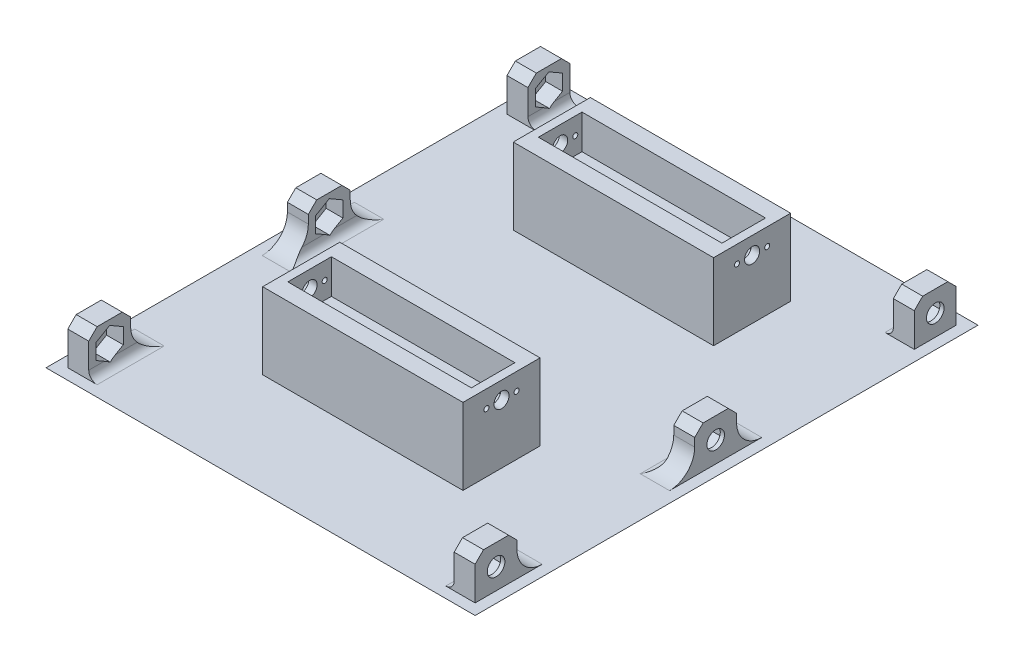
SolidWorks part; units mm, degrees
ref_plane "Front Plane" through (0, 0, 0) normal (0, 0, 1) x (1, 0, 0)
ref_plane "Top Plane" through (0, 0, 0) normal (0, 1, 0) x (1, 0, 0)
ref_plane "Right Plane" through (0, 0, 0) normal (1, 0, 0) x (0, 0, -1)
sketch "Sketch1" plane through (0, 0, 0) normal (0, 1, 0) x (1, 0, 0)
  line L1 (65.024, 76.2) -> (-65.024, 76.2)
  line L2 (65.024, 76.2) -> (65.024, -76.2)
  line L3 (65.024, -76.2) -> (-65.024, -76.2)
  line L4 (-65.024, 76.2) -> (-65.024, -76.2)
  line L5 (65.024, 76.2) -> (-65.024, -76.2) construction
  line L6 (65.024, -76.2) -> (-65.024, 76.2) construction
  point P0 (0, 0)
  dimension "D1" = 130.048
  dimension "D2" = 152.4
extrude "Boss-Extrude1" add sketch "Sketch1" along normal blind 2.54 contours L1 L4 L3 L2
chamfer "Chamfer1" distance 2.54 angle 45 4 edges at (0, 0, -76.2) (-65.024, 0, 0) (0, 0, 76.2) (65.024, 0, 0)
sketch "Sketch2" plane through (0, 2.54, 0) normal (0, 1, 0) x (1, 0, 0)
  line L1 (-27.813, 49.022) -> (27.813, 49.022)
  line L2 (-27.813, 49.022) -> (-27.813, 35.814)
  line L3 (-27.813, 35.814) -> (27.813, 35.814)
  line L4 (27.813, 49.022) -> (27.813, 35.814)
  line L5 (-27.813, 49.022) -> (27.813, 35.814) construction
  line L6 (-27.813, 35.814) -> (27.813, 49.022) construction
  line L7 (-27.813, -26.924) -> (27.813, -26.924)
  line L8 (-27.813, -26.924) -> (-27.813, -40.132)
  line L9 (-27.813, -40.132) -> (27.813, -40.132)
  line L10 (27.813, -26.924) -> (27.813, -40.132)
  line L11 (-27.813, -26.924) -> (27.813, -40.132) construction
  line L12 (-27.813, -40.132) -> (27.813, -26.924) construction
  line L13 (30.353, 54.102) -> (-30.353, 54.102)
  line L14 (30.353, 54.102) -> (30.353, 30.734)
  line L15 (30.353, 30.734) -> (-30.353, 30.734)
  line L16 (-30.353, 54.102) -> (-30.353, 30.734)
  line L17 (30.353, 54.102) -> (-30.353, 30.734) construction
  line L18 (30.353, 30.734) -> (-30.353, 54.102) construction
  line L19 (30.353, -45.212) -> (-30.353, -45.212)
  line L20 (30.353, -45.212) -> (30.353, -21.844)
  line L21 (30.353, -21.844) -> (-30.353, -21.844)
  line L22 (-30.353, -45.212) -> (-30.353, -21.844)
  line L23 (30.353, -45.212) -> (-30.353, -21.844) construction
  line L24 (30.353, -21.844) -> (-30.353, -45.212) construction
  line L26 (-65.024, -72.898) -> (65.024, -72.898) construction
  line L27 (-65.024, 76.2) -> (-65.024, -76.2) construction
  line L28 (65.024, 76.2) -> (65.024, -76.2) construction
  line L29 (65.024, -76.2) -> (-65.024, -76.2) construction
  point P0 (0, 42.418)
  point P5 (0, -33.528)
  point P10 (0, 42.418)
  point P16 (0, -33.528)
  dimension "D1" = 55.626
  dimension "D2" = 13.208
  dimension "D3" = 3.302
  dimension "D4" = 39.37
  dimension "D5" = 2.54
  dimension "D6" = 5.08
  dimension "D7" = 115.316
extrude "Boss-Extrude2" add sketch "Sketch2" along normal blind 23.114
extrude "Boss-Extrude3" add sketch "Sketch2<2>" along normal blind 12.7 contours L10 L7 L8 L9 | L4 L1 L2 L3 region at (0, 2.54, -42.418) region at (0, 2.54, 33.528)
sketch "Sketch2<2>" plane through (0, 2.54, 0) normal (0, 1, 0) x (1, 0, 0) same geometry as "Sketch2"
sketch "Sketch3" plane through (0, 0, 0) normal (1, 0, 0) x (0, 0, -1)
  line L0 (42.418, 25.654) -> (42.418, 15.24) construction
  line L1 (30.734, 25.654) -> (54.102, 25.654) construction
  line L2 (49.022, 15.24) -> (35.814, 15.24) construction
  line L3 (37.846, 20.447) -> (46.99, 20.447) construction
  line L4 (-21.844, 25.654) -> (30.734, 25.654) construction
  line L5 (4.445, 25.654) -> (4.445, 2.54) construction
  line L6 (76.2, 2.54) -> (-76.2, 2.54) construction
  line L7 (-28.956, 20.447) -> (-38.1, 20.447) construction
  line L8 (-33.528, 25.654) -> (-33.528, 15.24) construction
  circle A0 centre (42.418, 20.447) radius 2.286
  circle A1 centre (46.99, 20.447) radius 0.762
  circle A2 centre (37.846, 20.447) radius 0.762
  circle A3 centre (-28.956, 20.447) radius 0.762
  circle A4 centre (-38.1, 20.447) radius 0.762
  circle A5 centre (-33.528, 20.447) radius 2.286
  point P8 (42.418, 20.447)
  dimension "D1" = 1.524
  dimension "D2" = 4.572
  dimension "D3" = 7.62
extrude "Cut-Extrude1" cut sketch "Sketch3" against normal through all both and the other way through all
sketch "Sketch4" plane through (0, 2.54, 0) normal (0, 1, 0) x (1, 0, 0)
  line L0 (0, 76.2) -> (0, -76.2) construction
  line L1 (-61.722, 72.898) -> (-55.372, 72.898)
  line L2 (-61.722, 72.898) -> (-61.722, 60.198)
  line L3 (-61.722, 60.198) -> (-55.372, 60.198)
  line L4 (-55.372, 72.898) -> (-55.372, 60.198)
  line L5 (-61.722, 72.898) -> (-55.372, 60.198) construction
  line L6 (-61.722, 60.198) -> (-55.372, 72.898) construction
  line L7 (-61.722, 6.35) -> (-55.372, 6.35)
  line L8 (-61.722, 6.35) -> (-61.722, -6.35)
  line L9 (-61.722, -6.35) -> (-55.372, -6.35)
  line L10 (-55.372, 6.35) -> (-55.372, -6.35)
  line L11 (-61.722, 6.35) -> (-55.372, -6.35) construction
  line L12 (-61.722, -6.35) -> (-55.372, 6.35) construction
  line L13 (-61.722, -60.198) -> (-55.372, -60.198)
  line L14 (-61.722, -60.198) -> (-61.722, -72.898)
  line L15 (-61.722, -72.898) -> (-55.372, -72.898)
  line L16 (-55.372, -60.198) -> (-55.372, -72.898)
  line L17 (-61.722, -60.198) -> (-55.372, -72.898) construction
  line L18 (-61.722, -72.898) -> (-55.372, -60.198) construction
  line L19 (65.024, 76.2) -> (-65.024, 76.2) construction
  line L20 (65.024, -76.2) -> (-65.024, -76.2) construction
  line L22 (61.722, -72.898) -> (55.372, -60.198) construction
  line L23 (61.722, -60.198) -> (55.372, -72.898) construction
  line L24 (61.722, -6.35) -> (55.372, 6.35) construction
  line L25 (61.722, 6.35) -> (55.372, -6.35) construction
  line L26 (61.722, 60.198) -> (55.372, 72.898) construction
  line L27 (61.722, 72.898) -> (55.372, 60.198) construction
  line L28 (55.372, -60.198) -> (55.372, -72.898)
  line L29 (61.722, -72.898) -> (55.372, -72.898)
  line L30 (61.722, -60.198) -> (61.722, -72.898)
  line L31 (61.722, -60.198) -> (55.372, -60.198)
  line L32 (55.372, 6.35) -> (55.372, -6.35)
  line L33 (61.722, -6.35) -> (55.372, -6.35)
  line L34 (61.722, 6.35) -> (61.722, -6.35)
  line L35 (61.722, 6.35) -> (55.372, 6.35)
  line L36 (55.372, 72.898) -> (55.372, 60.198)
  line L37 (61.722, 60.198) -> (55.372, 60.198)
  line L38 (61.722, 72.898) -> (61.722, 60.198)
  line L39 (61.722, 72.898) -> (55.372, 72.898)
  line L40 (-58.547, 60.198) -> (-58.547, -60.198) construction
  point P4 (-58.547, 66.548)
  point P9 (-58.547, 0)
  point P14 (-58.547, -66.548)
  point P21 (-58.547, 0)
  point P38 (58.547, -66.548)
  point P39 (58.547, 0)
  point P40 (58.547, 66.548)
  dimension "D1" = 12.7
  dimension "D2" = 6.35
  dimension "D3" = 123.444
  dimension "D4" = 145.796
extrude "Boss-Extrude4" add sketch "Sketch4" along normal blind 12.7
sketch "Sketch5" plane through (0, 0, 0) normal (1, 0, 0) x (0, 0, -1)
  line L0 (0, 15.24) -> (0, 2.54) construction
  line L1 (-6.35, 15.24) -> (6.35, 15.24) construction
  line L2 (76.2, 2.54) -> (-76.2, 2.54) construction
  line L3 (66.548, 15.24) -> (66.548, 2.54) construction
  line L4 (0, 4.124) -> (4.1275, 6.507)
  line L5 (4.1275, 6.507) -> (4.1275, 11.273)
  line L6 (4.1275, 11.273) -> (0, 13.656)
  line L7 (0, 13.656) -> (-4.1275, 11.273)
  line L8 (-4.1275, 11.273) -> (-4.1275, 6.507)
  line L9 (-4.1275, 6.507) -> (0, 4.124)
  line L10 (60.198, 15.24) -> (72.898, 15.24) construction
  line L11 (60.198, 2.54) -> (72.898, 2.54) construction
  line L12 (-66.548, 15.24) -> (-66.548, 2.54) construction
  line L13 (-72.898, 15.24) -> (-60.198, 15.24) construction
  line L14 (-72.898, 2.54) -> (-60.198, 2.54) construction
  line L16 (-66.548, 4.124) -> (-62.4205, 6.507)
  line L17 (-62.4205, 6.507) -> (-62.4205, 11.273)
  line L18 (-62.4205, 11.273) -> (-66.548, 13.656)
  line L19 (-66.548, 13.656) -> (-70.6755, 11.273)
  line L20 (-70.6755, 11.273) -> (-70.6755, 6.507)
  line L21 (-70.6755, 6.507) -> (-66.548, 4.124)
  line L22 (66.548, 4.124) -> (70.6755, 6.507)
  line L23 (70.6755, 6.507) -> (70.6755, 11.273)
  line L24 (70.6755, 11.273) -> (66.548, 13.656)
  line L25 (66.548, 13.656) -> (62.4205, 11.273)
  line L26 (62.4205, 11.273) -> (62.4205, 6.507)
  line L27 (62.4205, 6.507) -> (66.548, 4.124)
  circle A0 centre (0, 8.89) radius 4.1275 construction
  circle A1 centre (0, 8.89) radius 2.667
  circle A2 centre (-66.548, 8.89) radius 4.1275 construction
  circle A3 centre (66.548, 8.89) radius 4.1275 construction
  circle A4 centre (-66.548, 8.89) radius 2.667
  circle A5 centre (66.548, 8.89) radius 2.667
  point P7 (-2.0637, 5.3155)
  dimension "D2" = 5.334
  dimension "D1" = 8.255
extrude "Cut-Extrude2" cut sketch "Sketch5" against normal through all both and the other way through all contours A4 | A1 | A5 region at (0, 8.89, 0) region at (0, 8.89, 66.548) region at (0, 8.89, -66.548)
extrude "Cut-Extrude3" cut sketch "Sketch5<3>" against normal offset from surface 1.27 and the other way offset from surface 1.27 up to face at (-61.722, 8.89, 63.881) other way up to face at (61.722, 8.89, 69.215)
sketch "Sketch5<3>" plane through (0, 0, 0) normal (1, 0, 0) x (0, 0, -1) same geometry as "Sketch5"
fillet "Fillet1" radius 7.62 6 edges at (58.547, 2.54, 60.198) (58.547, 2.54, 6.35) (58.547, 2.54, -6.35) (-58.547, 2.54, 60.198) (-58.547, 2.54, 6.35) (-58.547, 2.54, -6.35)
fillet "Fillet2" radius 2.54 6 edges at (55.372, 2.54, 62.738) (-55.372, 2.54, 62.738) (-55.372, 2.54, 0) (55.372, 2.54, 0) (55.372, 2.54, -66.548) (-55.372, 2.54, -66.548)
chamfer "Chamfer2" distance 2.54 angle 45 12 edges at (58.547, 15.24, -72.898) (-58.547, 15.24, -72.898) (-58.547, 15.24, 72.898) (58.547, 15.24, 72.898) (-58.547, 15.24, 60.198) (-58.547, 15.24, -60.198) (-58.547, 15.24, -6.35) (-58.547, 15.24, 6.35) (58.547, 15.24, 60.198) (58.547, 15.24, 6.35) (58.547, 15.24, -6.35) (58.547, 15.24, -60.198)
